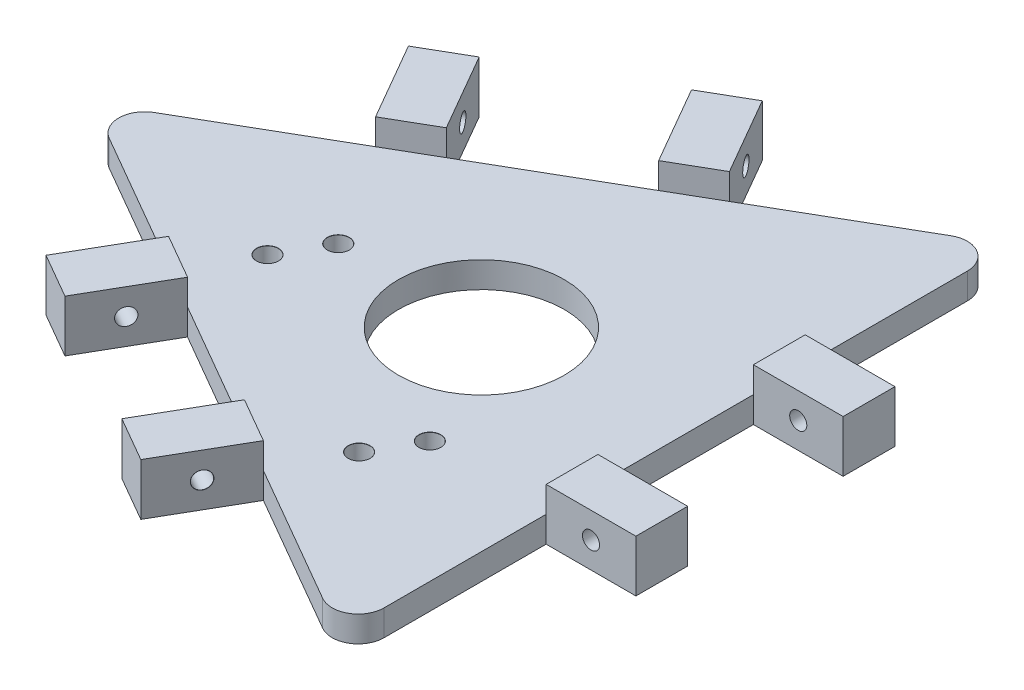
SolidWorks part; units mm, degrees
material "ABS"
ref_plane "Front" through (0, 0, 0) normal (0, 0, 1) x (1, 0, 0)
ref_plane "Top" through (0, 0, 0) normal (0, 1, 0) x (1, 0, 0)
ref_plane "Right" through (0, 0, 0) normal (1, 0, 0) x (0, 0, -1)
sketch "Sketch2" plane through (0, 0, 0) normal (0, 1, 0) x (0, 0, -1)
  line L0 (0, 0) -> (0, 70) construction
  line L1 (0, 0) -> (-60.6218, -35) construction
  line L2 (-60.6218, -30) -> (-44.976, -2.9006)
  line L3 (4.3301, 67.5) -> (19.976, 40.4006)
  line L4 (56.2917, -37.5) -> (25, -37.5)
  line L5 (0, 0) -> (-23.8157, 13.75) construction
  line L9 (-44.976, -2.9006) -> (-59.976, 5.7596)
  line L10 (-39.976, 5.7596) -> (-54.976, 14.4199)
  line L11 (-59.976, 5.7596) -> (-54.976, 14.4199)
  line L12 (-24.976, 31.7404) -> (-39.976, 40.4006)
  line L13 (-34.976, 49.0609) -> (-39.976, 40.4006)
  line L14 (-19.976, 40.4006) -> (-34.976, 49.0609)
  line L17 (19.976, 40.4006) -> (34.976, 49.0609)
  line L18 (34.976, 49.0609) -> (39.976, 40.4006)
  line L19 (24.976, 31.7404) -> (39.976, 40.4006)
  line L20 (39.976, 5.7596) -> (54.976, 14.4199)
  line L21 (59.976, 5.7596) -> (54.976, 14.4199)
  line L22 (44.976, -2.9006) -> (59.976, 5.7596)
  line L25 (25, -37.5) -> (25, -54.8205)
  line L26 (25, -54.8205) -> (15, -54.8205)
  line L27 (15, -37.5) -> (15, -54.8205)
  line L28 (-25, -37.5) -> (-25, -54.8205)
  line L29 (-25, -54.8205) -> (-15, -54.8205)
  line L30 (-15, -37.5) -> (-15, -54.8205)
  line L32 (-39.976, 5.7596) -> (-24.976, 31.7404)
  line L33 (-19.976, 40.4006) -> (-4.3301, 67.5)
  line L34 (24.976, 31.7404) -> (39.976, 5.7596)
  line L35 (44.976, -2.9006) -> (60.6218, -30)
  line L36 (15, -37.5) -> (-15, -37.5)
  line L37 (-25, -37.5) -> (-56.2917, -37.5)
  line L38 (-44.976, -2.9006) -> (-39.976, 5.7596)
  line L39 (-19.976, 40.4006) -> (-24.976, 31.7404)
  line L40 (19.976, 40.4006) -> (24.976, 31.7404)
  line L41 (44.976, -2.9006) -> (39.976, 5.7596)
  line L42 (25, -37.5) -> (15, -37.5)
  line L43 (-25, -37.5) -> (-15, -37.5)
  line L46 (-21.0862, -18.0213) -> (-18.0112, -12.6952) construction
  line L47 (5.0638, 27.2718) -> (1.9888, 21.9458) construction
  line L50 (-21.0862, -18.0213) -> (-18.0112, -12.6952)
  line L51 (5.0638, 27.2718) -> (1.9888, 21.9458)
  line L57 (-11.7414, -2.8357) -> (-12.1744, -2.5857) construction
  line L58 (2.5964, 21.9981) -> (-17.7527, -13.2476) construction
  line L59 (-4.5724, 10.5814) -> (-17.7612, -12.2622) construction
  arc A0 (-60.6218, -30) -> (-56.2917, -37.5) centre (-56.2917, -32.5) ccw
  arc A1 (60.6218, -30) -> (56.2917, -37.5) centre (56.2917, -32.5) cw
  arc A2 (4.3301, 67.5) -> (-4.3301, 67.5) centre (0, 65) ccw
  circle A3 centre (-56.2917, -32.5) radius 5 construction
  dimension "D4" = 10
  dimension "D1" = 90
  dimension "D2" = 50
  dimension "D3" = 70
  dimension "D7" = 10
  dimension "D8" = 15
extrude "Boss-Extrude1" add sketch "Sketch2" along normal blind 5 contours L3 A2 L33 L39 L32 L38 L2 A0 L37 L43 L36 L42 L4 A1 L35 L41 L34 L40
extrude "Boss-Extrude3" add sketch "Sketch2<7>" along normal blind 10 contours L41 L22 L21 L20 | L17 L40 L19 L18 region at (-40.4006, 0, -29.976) region at (-5.7596, 0, -49.976)
sketch "Sketch2<7>" plane through (0, 0, 0) normal (0, 1, 0) x (0, 0, -1) same geometry as "Sketch2"
sketch "Sketch10" plane through (-21.6506, 0, 12.5) normal (-0.866, 0, 0.5) x (0.5, 0, 0.866)
  line L1 (-46.1603, 5) -> (-37.5, 5) construction
  line L2 (-54.8205, 5) -> (-46.1603, 5) construction
  line L9 (-54.8205, 10) -> (-54.8205, 0) construction
  line L11 (-46.1603, 5) -> (-46.1603, 10) construction
  line L12 (-37.5, 10) -> (-54.8205, 10) construction
  line L14 (-46.1603, 5) -> (-46.1603, 0) construction
  line L15 (-37.5, 0) -> (-54.8205, 0) construction
  point P0 (-46.1603, 5)
  dimension "D1" = 180
hole_wizard "Tap Drill for M4 Tap1" positions "Sketch10" profile "Sketch11" hole size "M4" standard "ISO" end condition through all
sketch "Sketch11" plane through (-44.7308, 5, -27.476) normal (0, 1, 0) x (0.5, 0, 0.866)
  line L0 (0, 0) -> (0, 88.1218)
  line L1 (0, 88.1218) -> (1.65, 88.1218)
  line L2 (1.65, 88.1218) -> (1.65, 0.025)
  line L3 (1.65, 0.025) -> (1.675, 0)
  line L5 (1.675, 0) -> (0, 0)
  line L6 (-1.65, 0.025) -> (-1.675, 0) construction
  line L11 (0, -6.35) -> (0, 107.95) construction
  dimension "Thru Hole Dia." = 3.3
  dimension "Thru Hole Depth" = 88.1218
  dimension "Near C'Sink Dia." = 3.35
  dimension "Near C'Sink Angle" = 90
pattern_circular "CirPattern1" count 3 every 120 about axis through (0, 5, 0) along (0, 1, 0) of "Boss-Extrude3", "Tap Drill for M4 Tap1"
sketch "Sketch13" plane through (0, 0, 0) normal (0, -1, 0) x (1, 0, 0)
  line L0 (-18.75, 32.476) -> (0, 0) construction
  line L1 (0, 0) -> (37.5, 0) construction
  line L2 (-5.7596, 39.976) -> (-31.7404, 24.976) construction
  line L3 (37.5, -15) -> (37.5, 15) construction
  line L4 (-31.7404, -24.976) -> (-5.7596, -39.976) construction
  line L5 (0, 0) -> (-18.75, -32.476) construction
  circle A1 centre (0.007, 0.0121) radius 16
  circle A2 centre (0, 0) radius 7.6921 construction
  point P3 (0, 0)
  point P4 (-18.75, 32.476)
  point P5 (37.5, 0)
  point P8 (-18.75, -32.476)
extrude "Cut-Extrude1" cut sketch "Sketch13" against normal through all contours A1
sketch "Sketch16" plane through (0, 5, 0) normal (0, 1, 0) x (1, 0, 0)
  arc A0 (-29.7754, -0.0725) -> (-28.5754, 2.0059) centre (-27.7898, 0.1667) ccw construction
  arc A1 (-34.7754, -8.7328) -> (-33.5754, -6.6543) centre (-32.7898, -8.4936) ccw construction
  arc A2 (16.0249, -23.7441) -> (14.8249, -25.8225) centre (14.0392, -23.9833) ccw construction
  arc A3 (11.0249, -32.4043) -> (9.8249, -34.4828) centre (9.0392, -32.6436) ccw construction
  arc A4 (-29.7754, -0.0725) -> (-28.5754, 2.0059) centre (-27.7898, 0.1667) ccw
  arc A5 (-34.7754, -8.7328) -> (-33.5754, -6.6543) centre (-32.7898, -8.4936) ccw
  arc A6 (16.0249, -23.7441) -> (14.8249, -25.8225) centre (14.0392, -23.9833) ccw
  arc A7 (11.0249, -32.4043) -> (9.8249, -34.4828) centre (9.0392, -32.6436) ccw
  point P0 (-27.7898, 0.1667)
  point P3 (-32.7898, -8.4936)
  point P6 (14.0392, -23.9833)
  point P9 (9.0392, -32.6436)
hole_wizard "Tap Drill for M5 Tap1" positions "Sketch16" profile "Sketch18" hole size "M5" standard "ISO" end condition through all
sketch "Sketch18" plane through (-27.7898, 5, -0.1667) normal (1, 0, 0) x (0, 0, 1)
  line L0 (0, 0) -> (0, 5)
  line L1 (0, 5) -> (2.1, 5)
  line L2 (2.1, 5) -> (2.1, 0.025)
  line L3 (2.1, 0.025) -> (2.125, 0)
  line L5 (2.125, 0) -> (0, 0)
  line L6 (-2.1, 0.025) -> (-2.125, 0) construction
  line L11 (0, -6.35) -> (0, 107.95) construction
  dimension "Thru Hole Dia." = 4.2
  dimension "Thru Hole Depth" = 5
  dimension "Near C'Sink Dia." = 4.25
  dimension "Near C'Sink Angle" = 90
